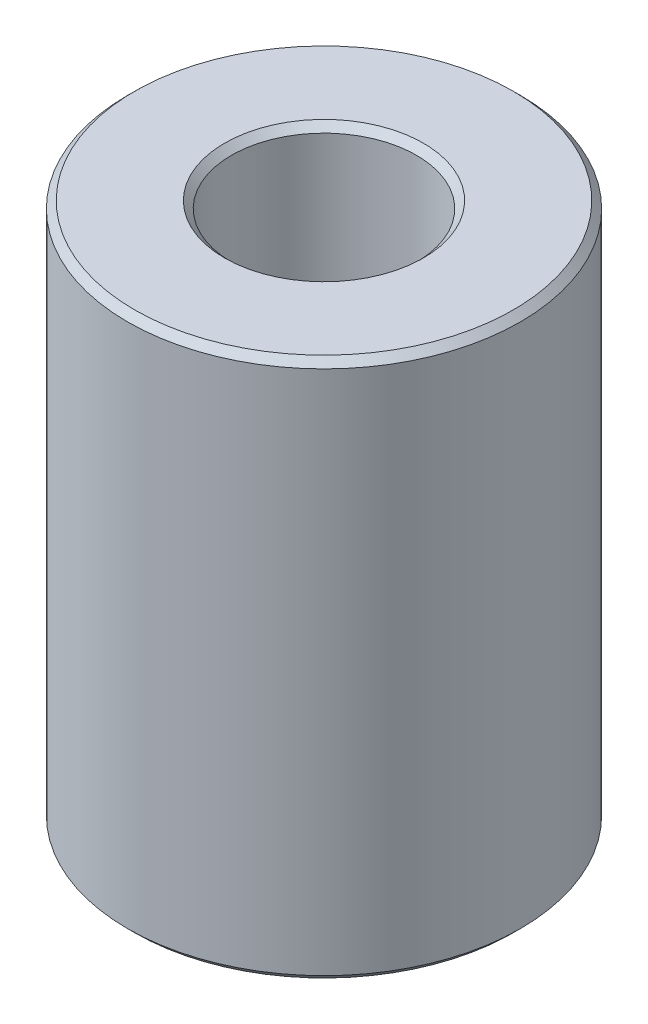
SolidWorks part; units mm, degrees
ref_plane "Front Plane" through (0, 0, 0) normal (0, 0, 1) x (1, 0, 0)
ref_plane "Top Plane" through (0, 0, 0) normal (0, 1, 0) x (1, 0, 0)
ref_plane "Right Plane" through (0, 0, 0) normal (1, 0, 0) x (0, 0, -1)
sketch "Sketch1" plane through (0, 0, 0) normal (0, 1, 0) x (1, 0, 0)
  circle A0 centre (0, 0) radius 55
  dimension "SLEEVE_OD" = 110
extrude "Boss-Extrude1" add sketch "Sketch1" along normal blind 151.1144
sketch "Sketch2" plane through (0, 0, 0) normal (0, 1, 0) x (1, 0, 0)
  circle A0 centre (0, 0) radius 25.9111
  dimension "BORE_D" = 51.8222
extrude "Cut-Extrude1" cut sketch "Sketch2" along normal through all
chamfer "Chamfer1" distance 1.9522 angle 45 4 edges at (0, 151.1144, 25.9111) (0, 0, 25.9111) (0, 0, 55) (0, 151.1144, 55)
